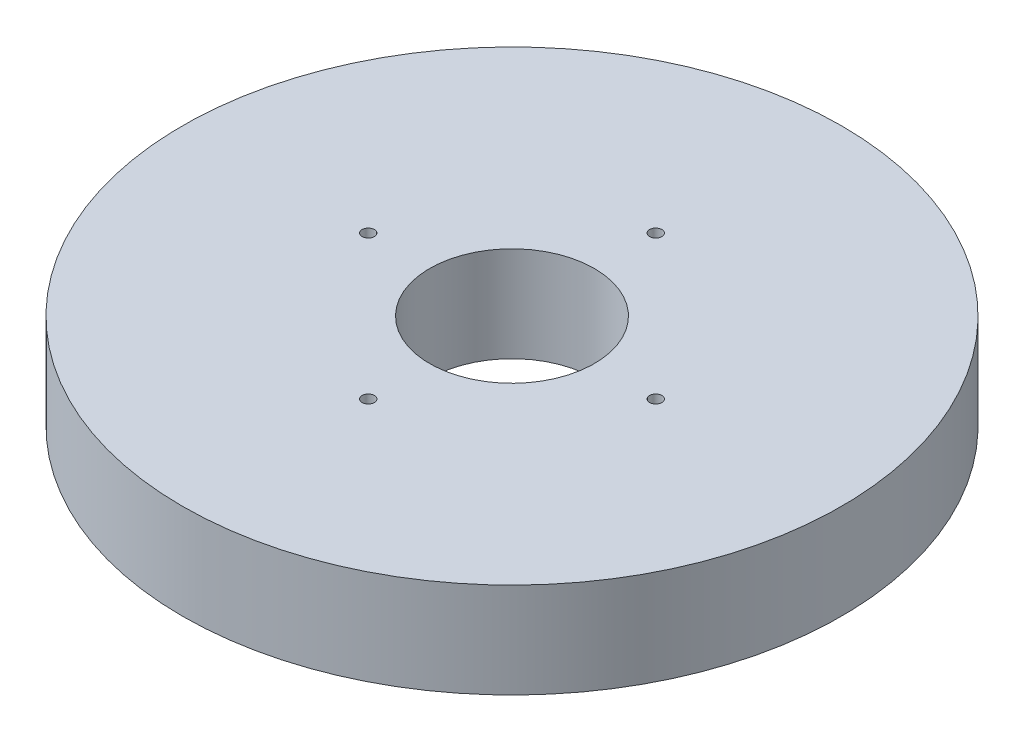
SolidWorks part; units mm, degrees
ref_plane "Front Plane" through (0, 0, 0) normal (0, 0, 1) x (1, 0, 0)
ref_plane "Top Plane" through (0, 0, 0) normal (0, 1, 0) x (1, 0, 0)
ref_plane "Right Plane" through (0, 0, 0) normal (1, 0, 0) x (0, 0, -1)
sketch "Sketch1" plane through (0, 0, 0) normal (0, 1, 0) x (1, 0, 0)
  circle A0 centre (0, 0) radius 90
  dimension "FLANGE_OD" = 180
extrude "Boss-Extrude1" add sketch "Sketch1" along normal blind 26
sketch "Sketch2" plane through (0, 0, 0) normal (0, 1, 0) x (1, 0, 0)
  circle A0 centre (0, 0) radius 22.5
  dimension "BORE_D" = 45
extrude "Cut-Extrude1" cut sketch "Sketch2" along normal through all
sketch "Sketch3" plane through (0, 26, 0) normal (0, 1, 0) x (1, 0, 0)
  circle A0 centre (0, 0) radius 39.2513 construction
  circle A1 centre (-39.2513, 0) radius 1.6778
  dimension "BOLT_D" = 3.3557
  dimension "BOLT_PCD" = 78.5026
extrude "Cut-Extrude2" cut sketch "Sketch3" against normal blind 18.4355
pattern_circular "CirPattern1" count 4 over 360 about axis through (0, 0, 0) along (0, 1, 0) of "Cut-Extrude2"
